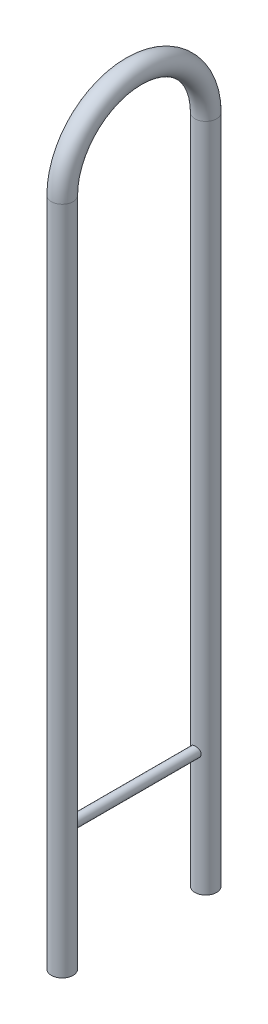
SolidWorks part; units mm, degrees
ref_plane "Front Plane" through (0, 0, 0) normal (1, 0, 0) x (0, 1, 0)
ref_plane "Top Plane" through (0, 0, 0) normal (0, 0, 1) x (0, 1, 0)
ref_plane "Right Plane" through (0, 0, 0) normal (0, 1, 0) x (-1, 0, 0)
sketch "Sketch2" plane through (0, 0, 0) normal (1, 0, 0) x (0, 1, 0)
  line L0 (0, 89.789) -> (-838.2, 89.789)
  line L1 (0, -89.789) -> (-838.2, -89.789)
  line L2 (-685.8, 89.789) -> (-685.8, -89.789)
  arc A0 (0, 89.789) -> (0, -89.789) centre (0, 0) cw
  point P8 (0, 0)
  dimension "D1" = 89.789
  dimension "D2" = 838.2
  dimension "D3" = 152.4
sweep "Sweep1" add path "Sketch2" circular profile diameter 27.178 parameters "D3"=27.178
sweep "Sweep2" add path "Sketch2<3>" circular profile diameter 12.7 parameters "D3"=12.7
sketch "Sketch2<3>" plane through (0, 0, 0) normal (1, 0, 0) x (0, 1, 0) same geometry as "Sketch2"
shell "Shell1" thickness 1.524 removed face at (0, -838.2, -103.378) removed face at (0, -838.2, 103.378)
